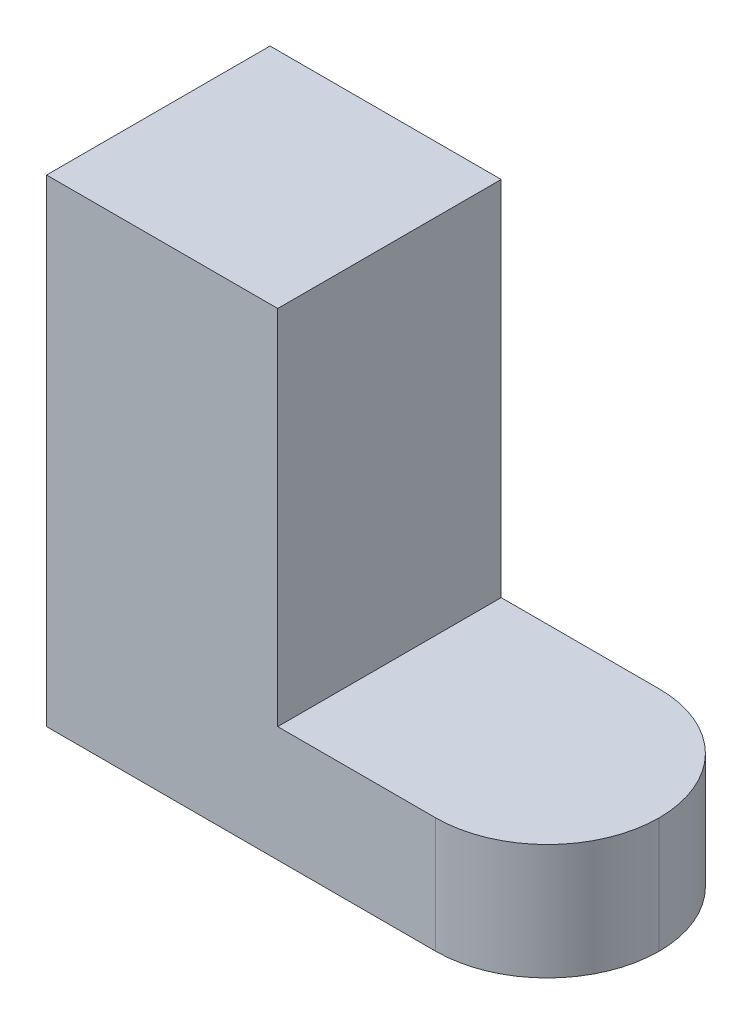
SolidWorks part; units mm, degrees
ref_plane "Přední rovina" through (0, 0, 0) normal (0, 0, 1) x (1, 0, 0)
ref_plane "Horní rovina" through (0, 0, 0) normal (0, 1, 0) x (1, 0, 0)
ref_plane "Pravá rovina" through (0, 0, 0) normal (1, 0, 0) x (0, 0, -1)
sketch "Skica2" plane through (0, 0, 0) normal (0, 0, 1) x (1, 0, 0)
  line L0 (0, 0) -> (65, 0)
  line L1 (65, 0) -> (65, 15)
  line L2 (65, 15) -> (30, 15)
  line L3 (30, 15) -> (30, 62)
  line L4 (30, 62) -> (0, 62)
  line L5 (0, 62) -> (0, 0)
  dimension "D1" = 62
  dimension "D2" = 30
  dimension "D3" = 15
  dimension "D4" = 65
extrude "Přidat vysunutím1" add sketch "Skica2" along normal mid plane 29
fillet "Zaoblit1" radius 14.5 2 edges at (65, 7.5, -14.5) (65, 7.5, 14.5)
